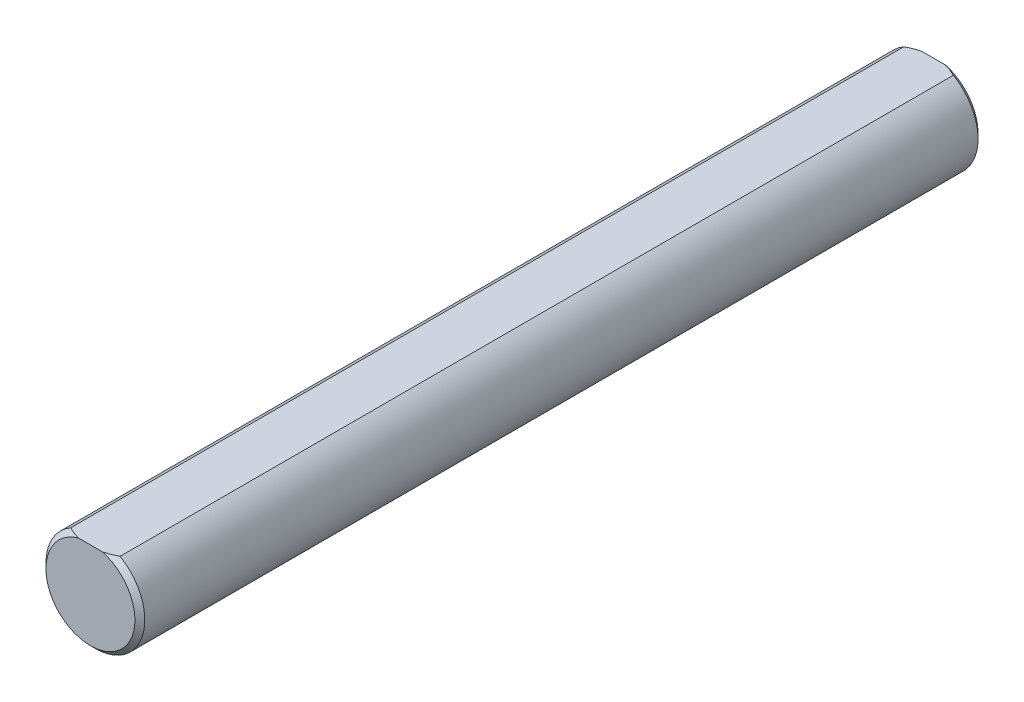
SolidWorks part; units mm, degrees
ref_plane "Front Plane" through (0, 0, 0) normal (0, 0, 1) x (1, 0, 0)
ref_plane "Top Plane" through (0, 0, 0) normal (0, 1, 0) x (1, 0, 0)
ref_plane "Right Plane" through (0, 0, 0) normal (1, 0, 0) x (0, 0, -1)
sketch "Sketch1" plane through (0, 0, 0) normal (0, 0, 1) x (1, 0, 0)
  line L0 (-1.5875, 2.7496) -> (1.5875, 2.7496) construction
  circle A1 centre (0, 0) radius 3.175 construction
  dimension "Diameter" = 6.35
  dimension "Flat Width" = 3.175
sketch "Sketch2" plane through (0, 0, 0) normal (1, 0, 0) x (0, 0, -1)
  line L0 (-27.08, 3.175) -> (27.08, 3.175) construction
  line L1 (0, 3.175) -> (0, -3.175) construction
  line L2 (0, 3.175) -> (0, -3.175) construction
  line L3 (-27.08, 3.175) -> (-27.08, -3.175) construction
  line L4 (-27.08, -3.175) -> (27.08, -3.175) construction
  point P2 (0, 3.175)
  point P3 (14.38, 3.175)
  point P4 (-14.38, 3.175)
  dimension "Length" = 54.16
  dimension "D2" = 12.7
  dimension "D1" = 12.7
  dimension "D-Profile Length" = 54.16
sketch "Sketch3" plane through (0, 0, 0) normal (0, 0, 1) x (1, 0, 0)
  circle A1 centre (0, 0) radius 3.175 construction
  circle A3 centre (0, 0) radius 3.175
extrude "Boss-Extrude2" add sketch "Sketch3" along normal up to vertex (27.08 mm away) and the other way up to vertex (27.08 mm away) up to point (0, 3.175, 27.08) other way up to point (0, 3.175, -27.08)
sketch "Sketch10" plane through (0, 0, 0) normal (0, 0, 1) x (1, 0, 0)
  line L0 (-1.5875, 2.7496) -> (1.5875, 2.7496)
  line L1 (0, 0) -> (0, 3.175) construction
  circle A0 centre (0, 0) radius 3.175 construction
  circle A1 centre (0, 0) radius 3.175 construction
  arc A2 (-1.5875, 2.7496) -> (1.5875, 2.7496) centre (0, 0) cw
extrude "Cut-Extrude5" cut sketch "Sketch10" against normal through all both and the other way through all
chamfer "Chamfer1" distance 0.3175 angle 45 2 edges at (0, -3.175, 27.08) (0, -3.175, -27.08)
equation "\"D1@Chamfer1\"= \"Diameter@Sketch1\" / 20"
equation "\"D1@Sketch2\"=\"Diameter@Sketch1\"*2"
equation "\"D2@Sketch2\"=\"D1@Sketch2\""
equation "\"D-Profile Length@Sketch2\"=\"Length@Sketch2\""
